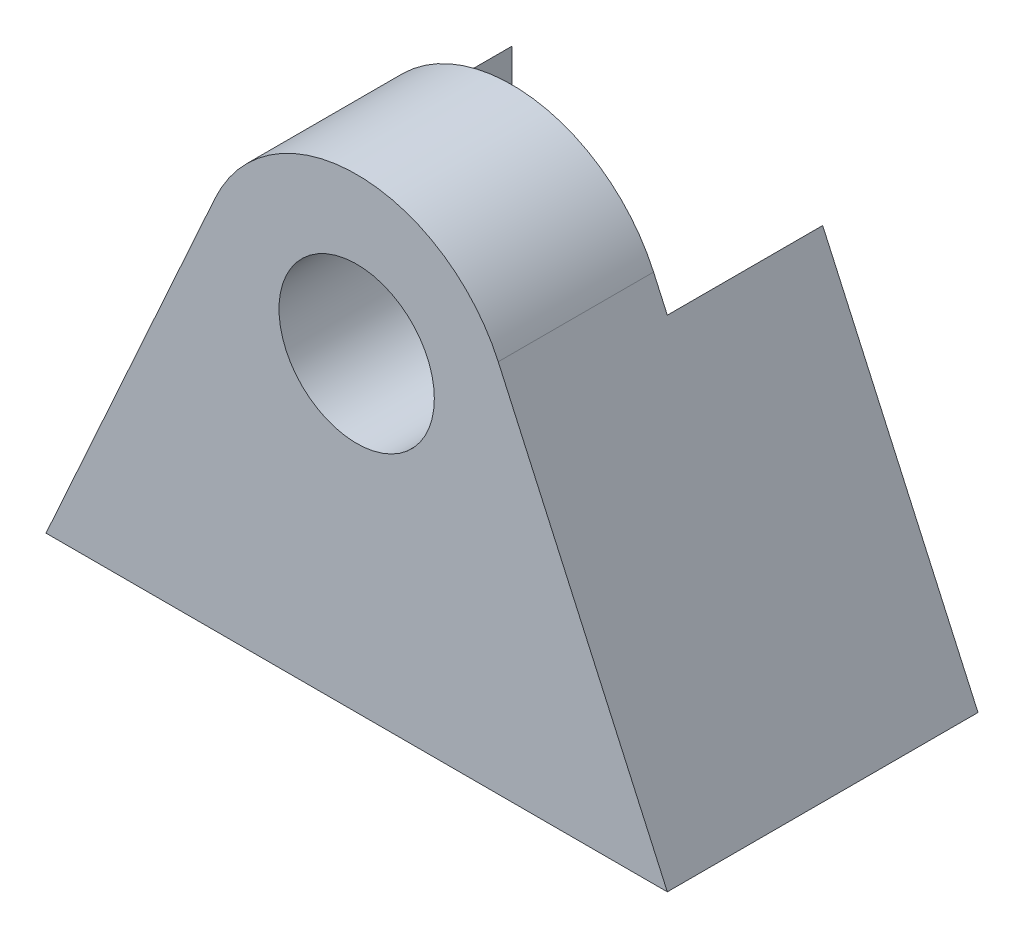
SolidWorks part; units mm, degrees
ref_plane "Front Plane" through (0, 0, 0) normal (0, 0, 1) x (1, 0, 0)
ref_plane "Top Plane" through (0, 0, 0) normal (0, 1, 0) x (1, 0, 0)
ref_plane "Right Plane" through (0, 0, 0) normal (1, 0, 0) x (0, 0, -1)
sketch "Sketch2" plane through (0, 0, 0) normal (0, 0, 1) x (1, 0, 0)
  line L0 (0, 0) -> (25.4, 0)
  line L1 (25.4, 0) -> (18.4876, 15.3126)
  line L2 (6.9124, 15.3126) -> (0, 0)
  circle A0 centre (12.7, 12.7) radius 3.175
  arc A1 (18.4876, 15.3126) -> (6.9124, 15.3126) centre (12.7, 12.7) ccw
  point P4 (21.5346, 16.8776)
  point P6 (0, 0)
  point P7 (0, 0)
  point P8 (31.6165, 19.05)
  point P9 (23.349, 39.8595)
  point P10 (24.6936, 25.4)
  point P13 (22.0535, 27.0066)
  point P14 (0, 0)
  point P15 (21.3776, 19.05)
  dimension "D2" = 6.35
  dimension "D3" = 6.35
  dimension "D1" = 12.7
  dimension "D4" = 25.4
extrude "Boss-Extrude2" add sketch "Sketch2" along normal mid plane 12.7
sketch "Sketch6" plane through (0, 0, 0) normal (0, 0, 1) x (1, 0, 0)
  line L0 (0, 0) -> (25.4, 0) construction
  line L5 (6.35, 19.05) -> (19.05, 19.05)
  line L6 (6.35, 19.05) -> (6.35, 6.35)
  line L7 (6.35, 6.35) -> (19.05, 6.35)
  line L8 (19.05, 19.05) -> (19.05, 6.35)
  line L9 (6.35, 19.05) -> (19.05, 6.35) construction
  line L10 (6.35, 6.35) -> (19.05, 19.05) construction
  point P0 (12.7, 12.7)
  dimension "D1" = 6.35
extrude "Cut-Extrude3" cut sketch "Sketch6" against normal blind 6.35
sketch "Sketch7" plane through (0, 6.35, 0) normal (0, 1, 0) x (1, 0, 0)
  line L0 (12.7, 6.35) -> (12.7, 0) construction
  line L1 (6.35, 6.35) -> (19.05, 6.35) construction
  line L2 (18.4876, 0) -> (6.9124, 0) construction
  line L3 (12.7, 3.175) -> (0, 3.175) construction
  line L4 (0, -6.35) -> (0, 6.35) construction
  circle A0 centre (6.35, 3.175) radius 1.905
  circle A1 centre (19.05, 3.175) radius 1.905
  point P12 (0, 0)
  point P13 (6.35, 3.175)
  dimension "D1" = 3.81
extrude "Cut-Extrude4" cut sketch "Sketch7" against normal blind 6.35
